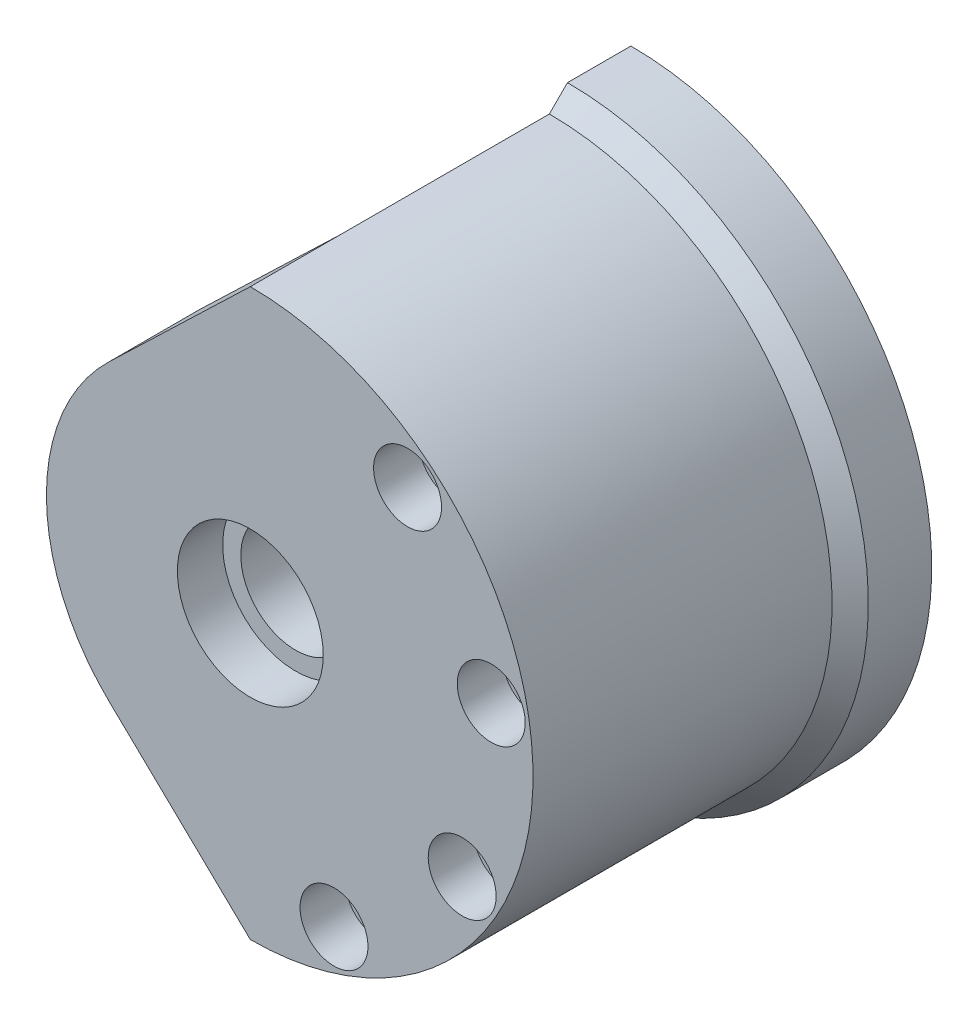
SolidWorks part; units mm, degrees
ref_plane "Piano frontale" through (0, 0, 0) normal (0, 0, 1) x (1, 0, 0)
ref_plane "Piano superiore" through (0, 0, 0) normal (0, 1, 0) x (1, 0, 0)
ref_plane "Piano destro" through (0, 0, 0) normal (1, 0, 0) x (0, 0, -1)
sketch "Schizzo1" plane through (0, 0, 0) normal (0, 0, 1) x (1, 0, 0)
  circle A0 centre (0, 0) radius 31.2
  circle A1 centre (0, 0) radius 22.5
  dimension "D1" = 45
  dimension "D2" = 62.4
extrude "Estrusione-Estrusione1" add sketch "Schizzo1" along normal blind 40
sketch "Schizzo2" plane through (0, 0, 40) normal (0, 0, 1) x (1, 0, 0)
  circle A0 centre (0, 0) radius 27 construction
  circle A1 centre (0, 27) radius 2.25
  dimension "D1" = 54
  dimension "D2" = 4.5
extrude "Taglio-Estrusione1" cut sketch "Schizzo2" against normal through all
pattern_circular "RipetizioneCircolare1" count 9 over 360 about axis through (0, 0, 40) along (0, 0, -1) of "Taglio-Estrusione1"
sketch "Schizzo3" plane through (0, 0, 0) normal (1, 0, 0) x (0, 0, -1)
  line L1 (-40, 31.2) -> (0, 31.2)
  line L2 (-40, 31.2) -> (-40, -31.2)
  line L3 (-40, -31.2) -> (0, -31.2)
  line L4 (0, 31.2) -> (0, -31.2)
extrude "Taglio-Estrusione2" cut sketch "Schizzo3" against normal blind 39
sketch "Schizzo4" plane through (0, 0, 40) normal (0, 0, 1) x (1, 0, 0)
  line L0 (0, 22.5) -> (0, -22.5)
  circle A0 centre (0, 0) radius 22.5
  arc A1 (0, -22.5) -> (0, 22.5) centre (0, 0) ccw construction
  arc M6 (0, 22.5) -> (0, -22.5) centre (0, 0) cw
extrude "Estrusione-Estrusione2" add sketch "Schizzo4" against normal blind 10 contours L0 M6 | L0 A0 region at (9.5493, 0, 40) region at (-9.5493, 0, 40)
fillet "Raccordo1" [suppressed] radius 10
sketch "Schizzo5" plane through (0, 0, 40) normal (0, 0, 1) x (1, 0, 0)
  circle A0 centre (0, 0) radius 8.05
  dimension "D1" = 16.1
extrude "Taglio-Estrusione3" cut sketch "Schizzo5" against normal blind 5
sketch "Schizzo6" plane through (0, 0, 35) normal (0, 0, 1) x (1, 0, 0)
  circle A0 centre (0, 0) radius 6.05
  circle A1 centre (0, 0) radius 8.05 construction
  dimension "D1" = 2
extrude "Taglio-Estrusione6" cut sketch "Schizzo6" against normal through all
sketch "Schizzo7" plane through (0, 0, 40) normal (0, 0, 1) x (1, 0, 0)
  circle A0 centre (17.3553, 20.6832) radius 3.75
  dimension "D1" = 7.5
extrude "Taglio-Estrusione7" cut sketch "Schizzo7" against normal blind 5
pattern_circular "RipetizioneCircolare2" count 9 over 360 about axis through (0, 0, 40) along (0, 0, -1) of "Taglio-Estrusione7"
sketch "Schizzo8" plane through (0, 0, 0) normal (0, 0, -1) x (-1, 0, 0)
  line L0 (0, 33.2) -> (0, -33.2)
  circle A0 centre (0, 0) radius 33.2
  circle A1 centre (0, 0) radius 31.2
  arc A2 (0, 31.2) -> (0, -31.2) centre (0, 0) ccw construction
  arc M5 (0, 31.2) -> (0, -31.2) centre (0, 0) ccw
  dimension "D1" = 2
extrude "Estrusione-Estrusione3" add sketch "Schizzo8" along normal blind 2 and the other way blind 5 contours L0 A0 M5 region at (0.7424, 32.2, 0)
chamfer "Smusso1" distance 2 angle 45 1 edges at (31.2, 0, 5)
fillet "Raccordo2" radius 4 1 edges at (22.5, 0, 30)
sketch "Schizzo9" plane through (0, 0, 40) normal (0, 0, 1) x (1, 0, 0)
  line L0 (0, 30.75) -> (0, 23.25)
  line L1 (0, 23.25) -> (0, 22.5) construction
  arc A0 (0, 23.25) -> (0, 30.75) centre (0, 27) ccw construction
  arc A1 (0, 30.75) -> (0, 23.25) centre (0, 27) cw
  arc M1 (0, 30.75) -> (0, 23.25) centre (0, 27) cw
extrude "Estrusione-Estrusione4" add sketch "Schizzo9" against normal up to surface (40 mm away) contours L0 M1 region at (1.5915, 27, 40) up to face at (7.1202, -26.1412, 0)
sketch "Schizzo10" plane through (0, 0, 40) normal (0, 0, 1) x (1, 0, 0)
  line L0 (0, 31.2) -> (-15.5874, 16.226)
  line L1 (0, -31.2) -> (-15.5874, -16.226)
  line L2 (0, 22.5) -> (0, 31.2)
  line L3 (0, -22.5) -> (0, -31.2)
  arc A0 (0, 22.5) -> (0, -22.5) centre (0, 0) ccw construction
  circle A1 centre (0, 0) radius 22.5
  line M3 (0, 31.2) -> (0, 22.5)
  arc M4 (0, 22.5) -> (0, -22.5) centre (0, 0) ccw
  line M5 (0, -22.5) -> (0, -31.2)
extrude "Estrusione-Estrusione5" add sketch "Schizzo10" against normal up to surface (10 mm away) contours L0 M3 M4 | L1 M5 M4 region at (-4.1402, 24.5493, 40) region at (-4.1402, -24.5493, 40) up to face at (6.05, 0, 30)
equation "\"A\"=30"
